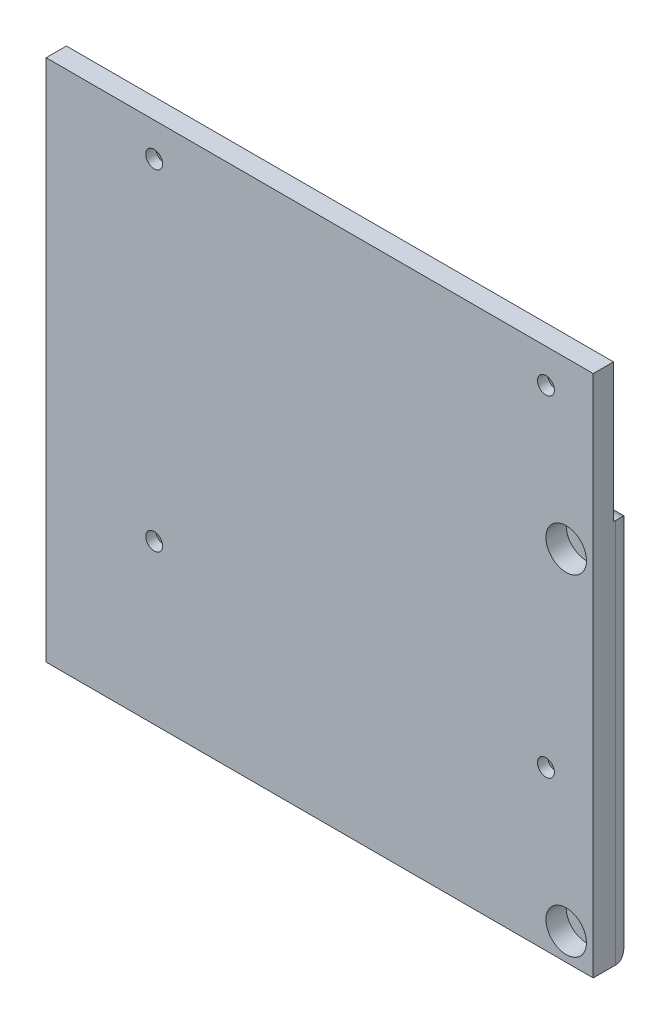
SolidWorks part; units mm, degrees
material "ABS"
ref_plane "Front Plane" through (0, 0, 0) normal (0, 0, 1) x (1, 0, 0)
ref_plane "Top Plane" through (0, 0, 0) normal (0, 1, 0) x (1, 0, 0)
ref_plane "Right Plane" through (0, 0, 0) normal (1, 0, 0) x (0, 0, -1)
sketch "Sketch1" plane through (0, 0, 0) normal (0, 0, 1) x (1, 0, 0)
  line L1 (115.6001, 71.6367) -> (196.6001, 71.6367)
  line L2 (115.6001, 71.6367) -> (115.6001, 14.6367)
  line L3 (115.6001, 14.6367) -> (196.6001, 14.6367)
  line L4 (196.6001, 71.6367) -> (196.6001, 14.6367)
  circle A1 centre (192.6001, 18.6367) radius 1.25
  circle A3 centre (192.6001, 67.6367) radius 1.25
  dimension "D3" = 2.5
  dimension "D4" = 2.5
  dimension "D1" = 57
  dimension "D2" = 81
extrude "Boss-Extrude1" add sketch "Sketch1" along normal blind 3.3
sketch "Sketch2" plane through (0, 0, 3.3) normal (0, 0, 1) x (1, 0, 0)
  line L1 (196.6001, 14.6367) -> (115.6001, 14.6367)
  line L2 (196.6001, 14.6367) -> (196.6001, 92.1367)
  line L3 (196.6001, 92.1367) -> (115.6001, 92.1367)
  line L4 (115.6001, 14.6367) -> (115.6001, 92.1367)
  circle A0 centre (192.6001, 67.6367) radius 1.25
  circle A1 centre (192.6001, 18.6367) radius 1.25
  dimension "D1" = 81
  dimension "D2" = 77.5
extrude "Boss-Extrude2" add sketch "Sketch2" along normal blind 3
sketch "Sketch3" plane through (0, 0, 6.3) normal (0, 0, 1) x (1, 0, 0)
  line L0 (196.6001, 92.1367) -> (115.6001, 92.1367) construction
  line L1 (131.6001, 87.1367) -> (189.6001, 87.1367)
  line L2 (131.6001, 87.1367) -> (131.6001, 38.1367)
  line L3 (131.6001, 38.1367) -> (189.6001, 38.1367)
  line L4 (189.6001, 87.1367) -> (189.6001, 38.1367)
  line L5 (196.6001, 14.6367) -> (196.6001, 92.1367) construction
  circle A0 centre (131.6001, 87.1367) radius 1.25
  circle A1 centre (189.6001, 87.1367) radius 1.25
  circle A2 centre (189.6001, 38.1367) radius 1.25
  circle A3 centre (131.6001, 38.1367) radius 1.25
  dimension "D5" = 2.5
  dimension "D1" = 58
  dimension "D2" = 49
  dimension "D3" = 5
  dimension "D4" = 7
extrude "Cut-Extrude1" cut sketch "Sketch3" against normal through all contours L1 A0 L2 | L2 A0 L1 | L4 A1 L1 | L1 A1 L4 | L3 A2 L4 | L4 A2 L3 | L2 A3 L3 | L3 A3 L2 region at (131.4233, 87.3136, 6.3) region at (132.1306, 86.6062, 6.3) region at (189.777, 87.3136, 6.3) region at (189.0696, 86.6062, 6.3) region at (132.1306, 38.6673, 6.3) region at (131.4233, 37.9599, 6.3) region at (189.777, 37.9599, 6.3) region at (189.0696, 38.6673, 6.3)
sketch "Sketch4" plane through (0, 0, 0) normal (0, 0, -1) x (-1, 0, 0)
  circle A0 centre (-189.6001, 38.1367) radius 6
  circle A1 centre (-131.6001, 38.1367) radius 6
  dimension "D1" = 12
  dimension "D2" = 12
extrude "Cut-Extrude2" cut sketch "Sketch4" against normal up to surface (3.3 mm away) up to face at (190.8501, 87.1367, 3.3)
sketch "Sketch5" plane through (0, 0, 3.3) normal (0, 0, -1) x (-1, 0, 0)
  line L0 (-196.6001, 92.1367) -> (-115.6001, 92.1367) construction
  line L1 (-187.2907, 87.1367) -> (-188.4454, 89.1367)
  line L2 (-188.4454, 89.1367) -> (-190.7548, 89.1367)
  line L3 (-190.7548, 89.1367) -> (-191.9095, 87.1367)
  line L4 (-191.9095, 87.1367) -> (-190.7548, 85.1367)
  line L5 (-190.7548, 85.1367) -> (-188.4454, 85.1367)
  line L6 (-188.4454, 85.1367) -> (-187.2907, 87.1367)
  line L7 (-129.2907, 87.1367) -> (-130.4454, 89.1367)
  line L8 (-130.4454, 89.1367) -> (-132.7548, 89.1367)
  line L9 (-132.7548, 89.1367) -> (-133.9095, 87.1367)
  line L10 (-133.9095, 87.1367) -> (-132.7548, 85.1367)
  line L11 (-132.7548, 85.1367) -> (-130.4454, 85.1367)
  line L12 (-130.4454, 85.1367) -> (-129.2907, 87.1367)
  line L13 (-130.4454, 40.1367) -> (-132.7548, 40.1367)
  line L14 (-132.7548, 40.1367) -> (-133.9095, 38.1367)
  line L15 (-133.9095, 38.1367) -> (-132.7548, 36.1367)
  line L16 (-132.7548, 36.1367) -> (-130.4454, 36.1367)
  line L17 (-130.4454, 36.1367) -> (-129.2907, 38.1367)
  line L18 (-129.2907, 38.1367) -> (-130.4454, 40.1367)
  line L19 (-187.2907, 38.1367) -> (-188.4454, 40.1367)
  line L20 (-188.4454, 40.1367) -> (-190.7548, 40.1367)
  line L21 (-190.7548, 40.1367) -> (-191.9095, 38.1367)
  line L22 (-191.9095, 38.1367) -> (-190.7548, 36.1367)
  line L23 (-190.7548, 36.1367) -> (-188.4454, 36.1367)
  line L24 (-188.4454, 36.1367) -> (-187.2907, 38.1367)
  circle A0 centre (-189.6001, 87.1367) radius 2 construction
  circle A1 centre (-131.6001, 87.1367) radius 2 construction
  circle A2 centre (-131.6001, 38.1367) radius 2 construction
  circle A3 centre (-189.6001, 38.1367) radius 2 construction
  dimension "D1" = 4
extrude "Cut-Extrude3" cut sketch "Sketch5" against normal blind 1.5
sketch "Sketch6" plane through (0, 0, 6.3) normal (0, 0, 1) x (1, 0, 0)
  circle A3 centre (192.6001, 67.6367) radius 3
  circle A4 centre (192.6001, 18.6367) radius 3
  dimension "D1" = 6
  dimension "D2" = 6
extrude "Cut-Extrude4" cut sketch "Sketch6" against normal blind 3
fillet "Fillet1" radius 3 4 edges at (156.1001, 14.6367, 0) (115.6001, 43.1367, 0) (156.1001, 71.6367, 0) (196.6001, 43.1367, 0)
